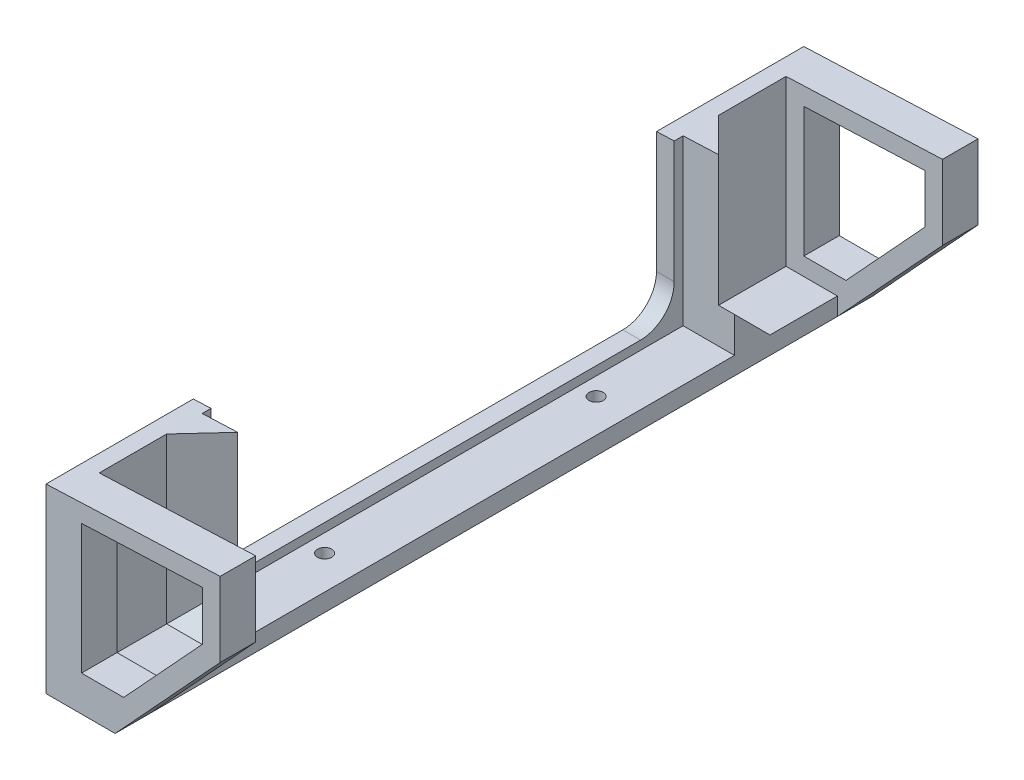
SolidWorks part; units mm, degrees
ref_plane "Front Plane" through (0, 0, 0) normal (0, 0, 1) x (1, 0, 0)
ref_plane "Top Plane" through (0, 0, 0) normal (0, 1, 0) x (1, 0, 0)
ref_plane "Right Plane" through (0, 0, 0) normal (1, 0, 0) x (0, 0, -1)
sketch "Sketch2" plane through (0, 0, 0) normal (0, 0, 1) x (1, 0, 0)
  line L0 (14.4779, -51.3446) -> (14.4779, -46.3446)
  line L2 (-5, -51.3446) -> (-5, -0.2052)
  line L4 (0, 0) -> (0, -46.3446)
  line L8 (44.0837, -19.205) -> (44.0837, 1.809)
  line L9 (-5, -51.3446) -> (14.4779, -51.3446)
  line L10 (14.4779, -46.3446) -> (0, -46.3446)
  line L11 (44.0837, 1.809) -> (-5, -0.2052)
  line L13 (19.0837, -46.3446) -> (0, -46.3446) construction
  line L18 (44.0837, -19.205) -> (14.4779, -51.3446)
  point P0 (0, 0)
  dimension "D2" = 46.3446
  dimension "D3" = 2.35
  dimension "D4" = 19.0837
  dimension "D5" = 45
  dimension "D8" = 5
  dimension "D9" = 5
  dimension "D12" = 25
extrude "Boss-Extrude1" add sketch "Sketch2" along normal blind 10 contours L9 L18 L8 L11 L2
extrude "Boss-Extrude6" add sketch "Sketch2<5>" against normal blind 41 contours L18 L13 L9 region at (-0.3532, -30.817, 0)
sketch "Sketch2<5>" plane through (0, 0, 0) normal (0, 0, 1) x (1, 0, 0) same geometry as "Sketch2"
sketch "Sketch6" plane through (0, 0, 0) normal (1, 0, 0) x (0, 0, -1)
  line L0 (41, 0) -> (41, -46.3446) construction
  line L1 (41, -46.3446) -> (0, -46.3446) construction
  line L2 (41, 0) -> (0, 0) construction
  line L5 (41, -17.1446) -> (33, -17.1446) construction
  line L6 (33, 0) -> (33, -17.1446) construction
  line L9 (31.5, 0) -> (41, 0)
  line L10 (41, 0) -> (41, -24.8446)
  line L12 (31.5, -34.3446) -> (31.5, 0)
  circle A0 centre (41, -34.3446) radius 8 construction
  arc A1 (31.5, -34.3446) -> (41, -24.8446) centre (41, -34.3446) ccw
  circle A2 centre (41, -34.3446) radius 9.5 construction
  point P13 (41, -26.3446)
  dimension "D2" = 16
  dimension "D1" = 12
  dimension "D4" = 9.2
  dimension "D5" = 8
  dimension "Margin" = 1.5
extrude "Cut-Extrude1" cut sketch "Sketch6" against normal up to next
sketch "Sketch7" plane through (0, 0, 0) normal (0, 0, -1) x (-1, 0, 0)
  line L10 (-39.0837, -17.2531) -> (-16.8915, -41.3446)
  line L11 (-16.8915, -41.3446) -> (-5, -41.3446)
  line L12 (-5, -41.3446) -> (-5, -4.799)
  line L13 (-5, -4.799) -> (-39.0837, -3.4004)
  line L14 (-39.0837, -3.4004) -> (-39.0837, -17.2531)
  line L15 (-39.0837, -17.2531) -> (-16.8915, -41.3446)
  line L17 (-5, -41.3446) -> (-5, -4.799)
  line L18 (-5, -4.799) -> (-39.0837, -3.4004)
  line L19 (-39.0837, -3.4004) -> (-39.0837, -17.2531)
  line L22 (-16.8915, -41.3446) -> (-5, -41.3446)
  dimension "D1" = 5
extrude "Cut-Extrude2" cut sketch "Sketch7" against normal up to next
ref_plane "Plane1" through (0, 0, -29) normal (0, 0, 1) x (1, 0, 0)
sketch "Sketch10" plane through (0, 0, -29) normal (0, 0, 1) x (1, 0, 0)
  line L0 (14.4779, -46.3446) -> (0, -46.3446) construction
  line L1 (14.4779, -46.3446) -> (0, -46.3446)
  line L2 (0, 0) -> (0, -46.3446) construction
  line L3 (0, 0) -> (0, -46.3446)
  line L4 (14.4779, -46.3446) -> (14.4779, -36.3446)
  line L5 (14.4779, -36.3446) -> (10, -36.3446)
  line L6 (10, -36.3446) -> (10, 0.4103)
  line L7 (0, 0) -> (10, 0.4103)
  line L8 (44.0837, 1.809) -> (0, 0) construction
  dimension "D1" = 10
  dimension "D2" = 10
extrude "Boss-Extrude9" add sketch "Sketch10" along normal blind 10
chamfer "Chamfer3" distance 10 angle 45 2 edges at (12.239, -36.3446, -19) (10, -17.9671, -19)
ref_plane "Plane2" through (0, 0, -96.75) normal (0, 0, -1) x (-1, 0, 0)
sketch "Sketch11" plane through (0, 0, -41) normal (0, 0, -1) x (-1, 0, 0)
  line L6 (5, -51.3446) -> (5, -43.8446)
  line L7 (5, -43.8446) -> (0, -43.8446)
  line L8 (0, -43.8446) -> (0, -46.3446)
  line L9 (0, -46.3446) -> (-14.4779, -46.3446)
  line L10 (-14.4779, -46.3446) -> (-14.4779, -51.3446)
  line L11 (-14.4779, -51.3446) -> (5, -51.3446)
  line L12 (5, -51.3446) -> (5, -43.8446)
  line L13 (5, -43.8446) -> (0, -43.8446)
  line L14 (0, -43.8446) -> (0, -46.3446)
  line L15 (0, -46.3446) -> (-14.4779, -46.3446)
  line L17 (-14.4779, -51.3446) -> (5, -51.3446)
  line L18 (-14.4779, -46.3446) -> (-14.4779, -51.3446)
  dimension "D1" = 0
extrude "Boss-Extrude10" add sketch "Sketch11" along normal up to surface (55.75 mm away) up to plane "Plane2"
sketch "Sketch12" plane through (0, -46.3446, 0) normal (0, 1, 0) x (1, 0, 0)
  line L0 (14.4779, 29) -> (10, 29) construction
  circle A0 centre (5, 58.5) radius 2
  dimension "D3" = 4
  dimension "D1" = 29.5
  dimension "D2" = 5
extrude "Cut-Extrude3" cut sketch "Sketch12" against normal up to next
mirror "Mirror3" about plane through (0, 0, -96.75) normal (0, 0, -1) of bodies 114
